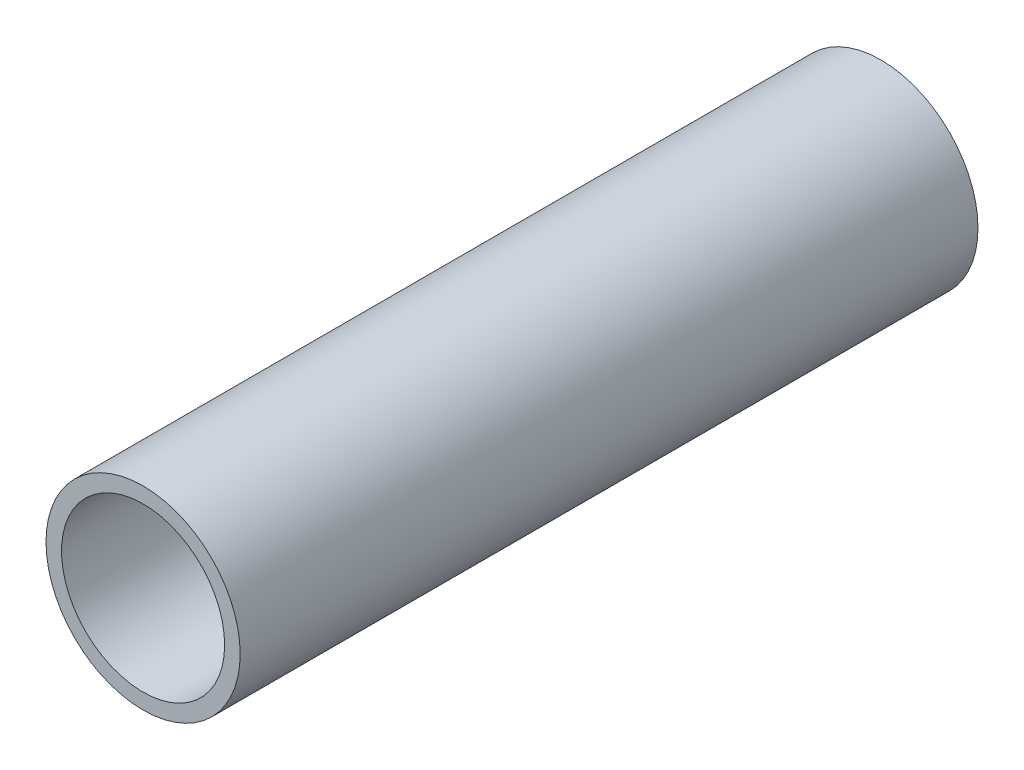
SolidWorks part; units mm, degrees
ref_plane "Front Plane" through (0, 0, 0) normal (0, 0, 1) x (1, 0, 0)
ref_plane "Top Plane" through (0, 0, 0) normal (0, 1, 0) x (1, 0, 0)
ref_plane "Right Plane" through (0, 0, 0) normal (1, 0, 0) x (0, 0, -1)
sketch "Sketch1" plane through (0, 0, 0) normal (0, 0, 1) x (1, 0, 0)
  circle A0 centre (33, 0) radius 2.5
  dimension "D1" = 5
extrude "Boss-Extrude1" add sketch "Sketch1" along normal blind 19
sketch "Sketch3" plane through (0, 0, 19) normal (0, 0, 1) x (1, 0, 0)
  circle A0 centre (33, 0) radius 1.6
  circle A1 centre (33, 0) radius 2.1
  dimension "D1" = 3.2
  dimension "D2" = 4.2
extrude "Cut-Extrude1" cut sketch "Sketch3" against normal up to next contours A0
extrude "Cut-Extrude2" cut sketch "Sketch3<3>" against normal blind 6
sketch "Sketch3<3>" plane through (0, 0, 19) normal (0, 0, 1) x (1, 0, 0) same geometry as "Sketch3"
ref_plane "Plane1" through (0, 0, 9.5) normal (0, 0, 1) x (1, 0, 0)
mirror "Mirror1" about plane through (0, 0, 9.5) normal (0, 0, 1) of "Cut-Extrude2"
equation "\"RingPostIn\"=5"
equation "\"D1@Sketch1\"=\"RingPostIn\""
equation "\"RingPinShaft\"= 5"
equation "\"CenterBearingOut\"=32"
equation "\"m3Thru\"=3.2"
equation "\"D1@Sketch3\"=\"m3Thru\""
equation "\"m3Insert\"=4.2"
equation "\"D2@Sketch3\"=\"m3Insert\""
